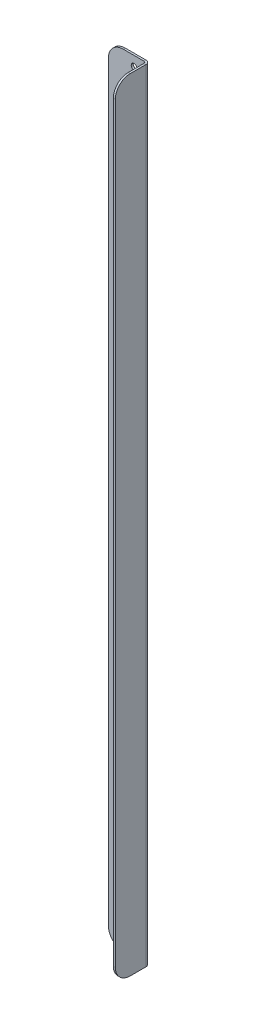
SolidWorks part; units mm, degrees
note: The reader was unsure of these and kept them because the rebuilt part matched: flange length of "Edge-Flange1".
material "AISI 316 Stainless Steel Sheet (SS)"
ref_plane "Front Plane" through (0, 0, 0) normal (0, 0, 1) x (1, 0, 0)
ref_plane "Top Plane" through (0, 0, 0) normal (0, 1, 0) x (1, 0, 0)
ref_plane "Right Plane" through (0, 0, 0) normal (1, 0, 0) x (0, 0, -1)
sketch "Sketch2" plane through (0, 0, 0) normal (0, 0, 1) x (1, 0, 0)
  line L1 (-20, -396) -> (20, -396)
  line L2 (-20, -396) -> (-20, 396)
  line L3 (-20, 396) -> (20, 396)
  line L4 (20, -396) -> (20, 396)
  line L5 (-20, -396) -> (20, 396) construction
  line L6 (-20, 396) -> (20, -396) construction
  point P0 (0, 0)
  dimension "D1" = 40
  dimension "D2" = 792
base flange "Base-Flange1" sketch "Sketch2" thickness 2 reverse thickness direction no parameters "D1"=1
edge flange "Edge-Flange1" sketch "Sketch9" flange angle 90 flange length 35 flange position material inside bend radius 2 thickness 2 relief rectangular parameters "D6"=10
sketch "Sketch9" plane through (20, 0, 0) normal (1, 0, 0) x (0, 1, 0)
  line L0 (-396, 0) -> (396, 0) construction
  line L1 (-396, 0) -> (396, 0)
  line L2 (-396, 0) -> (-396, 33)
  line L3 (-396, 33) -> (396, 33)
  line L4 (396, 33) -> (396, 0)
bend "EdgeBend1" bend radius 2 bend angle 90 parameters "D5"=1
hole_wizard "M5 Clearance Hole1" positions "Sketch10" profile "Sketch11" hole size "M5" standard "ISO" end condition through all
sketch "Sketch10" plane through (0, 0, 0) normal (0, 0, 1) x (1, 0, 0)
  circle A0 centre (6.0075, -386) radius 2.75 construction
  point P0 (6.0075, -386)
  point P3 (0, 0)
  point P4 (0, 0)
sketch "Sketch11" plane through (6.0075, -386, 0) normal (1, 0, 0) x (0, -1, 0)
  line L0 (0, 0) -> (0, 2)
  line L1 (0, 2) -> (2.9, 2)
  line L2 (2.9, 2) -> (2.9, 0)
  line L5 (2.9, 0) -> (0, 0)
  line L11 (0, -6.35) -> (0, 107.95) construction
  dimension "Thru Hole Dia." = 5.8
  dimension "Thru Hole Depth" = 2
pattern_linear "LPattern1" count 5 spacing 193 along (0, 1, 0) of "M5 Clearance Hole1"
fillet "Fillet1" radius 15 4 edges at (19, 396, 33) (-20, 396, -1) (-20, -396, -1) (19, -396, 33)
sketch "Bend-Lines1" [suppressed] plane through (0, 0, 0) normal (0, 1, 0) x (1, 0, 0)
sketch "Bounding-Box1" [suppressed] plane through (0, 0, 0) normal (0, 1, 0) x (1, 0, 0)
sheet metal parameters "Sheet-Metal1" thickness 2 parameters "D1"=1
flat pattern "Flat-Pattern1" [suppressed]
sketch "Bend-Lines2" plane through (0, 0, 0) normal (0, 1, 0) x (1, 0, 0)
sketch3d "Bounding-Box2" [suppressed]
  line L0 (-30, 390, 0) -> (-30, -390, 0) construction
  line L1 (30, 390, 0) -> (30, -390, 0) construction
  line L2 (-30, 390, 0) -> (30, 390, 0) construction
  line L3 (-30, -390, 0) -> (30, -390, 0) construction
sheet metal parameters "Sheet-Metal2" thickness 2 parameters "D1"=1
flat pattern "Flat-Pattern1"
sketch "Bend-Lines2" plane through (0, 0, 0) normal (0, 0, 1) x (1, 0, 0)
  line L0 (28.3562, -396) -> (28.3562, 396) construction
  line L1 (28.3562, -396) -> (28.3562, 396) construction
sketch3d "Bounding-Box2" [suppressed]
  line L0 (61.7124, 396, 0) -> (61.7124, -396, 0) construction
  line L1 (-30, 396, 0) -> (-30, -396, 0) construction
  line L2 (61.7124, 396, 0) -> (-30, 396, 0) construction
  line L3 (61.7124, -396, 0) -> (-30, -396, 0) construction
bend of the flat pattern "Flatten-<EdgeBend1>1"
sheet metal parameters "Sheet-Metal3" thickness 2 parameters "D1"=1
flat pattern "Flat-Pattern1"
sketch "Bend-Lines2" plane through (0, 0, 0) normal (0, 0, 1) x (1, 0, 0)
  line L0 (28.3562, -396) -> (28.3562, 396) construction
  line L1 (28.3562, -396) -> (28.3562, 396) construction
sketch3d "Bounding-Box2" [suppressed]
  line L0 (61.7124, 396, 0) -> (61.7124, -396, 0) construction
  line L1 (-30, 396, 0) -> (-30, -396, 0) construction
  line L2 (61.7124, 396, 0) -> (-30, 396, 0) construction
  line L3 (61.7124, -396, 0) -> (-30, -396, 0) construction
bend of the flat pattern "Flatten-<EdgeBend1>1"
sheet metal parameters "Sheet-Metal4" thickness 2 parameters "D1"=1
flat pattern "Flat-Pattern1"
sketch "Bend-Lines2" plane through (0, 0, 0) normal (0, 0, 1) x (1, 0, 0)
  line L0 (18.3562, -396) -> (18.3562, 396) construction
  line L1 (18.3562, -396) -> (18.3562, 396) construction
sketch3d "Bounding-Box2" [suppressed]
  line L0 (51.7124, -396, 0) -> (51.7124, 396, 0) construction
  line L1 (-20, -396, 0) -> (-20, 396, 0) construction
  line L2 (51.7124, -396, 0) -> (-20, -396, 0) construction
  line L3 (51.7124, 396, 0) -> (-20, 396, 0) construction
bend of the flat pattern "Flatten-<EdgeBend1>1"
